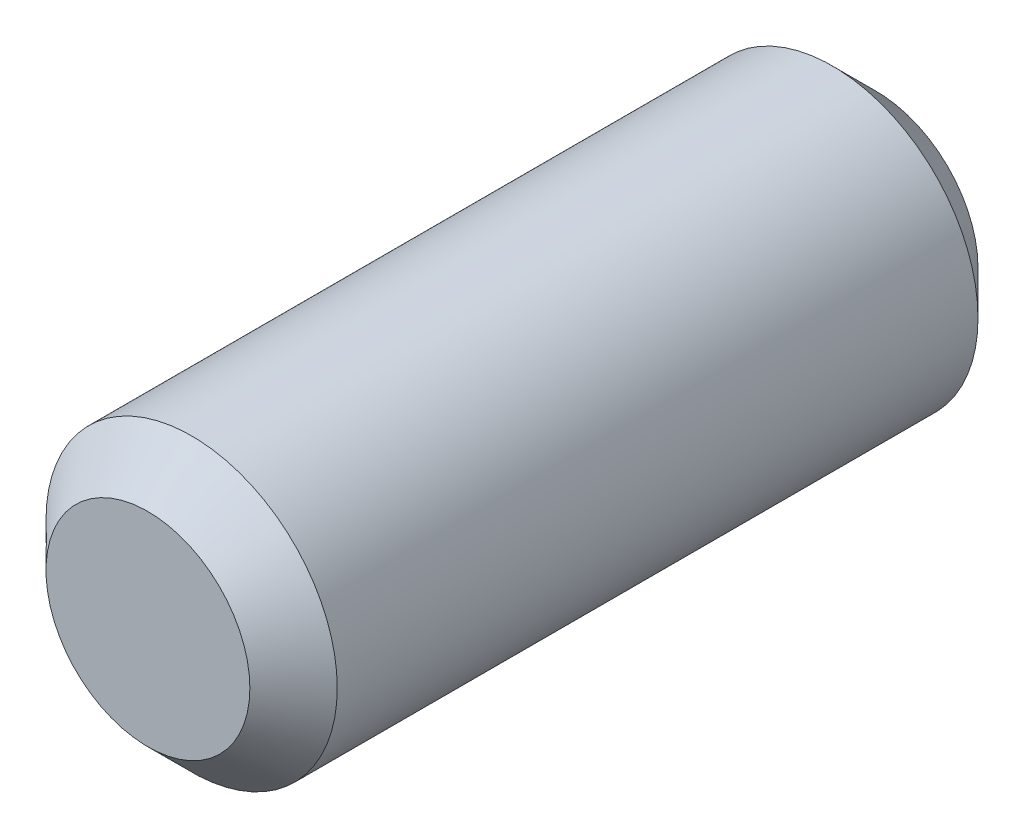
SolidWorks part; units mm, degrees
ref_plane "Plano frontal" through (0, 0, 0) normal (0, 0, 1) x (1, 0, 0)
ref_plane "Plano superior" through (0, 0, 0) normal (0, 1, 0) x (1, 0, 0)
ref_plane "Plano direito" through (0, 0, 0) normal (1, 0, 0) x (0, 0, -1)
sketch "Esboço1" plane through (0, 0, 0) normal (0, 0, 1) x (1, 0, 0)
  circle A0 centre (0, 0) radius 1
  dimension "D1" = 2
extrude "Ressalto-extrusão1" add sketch "Esboço1" along normal blind 2.5 and the other way blind 2.5
chamfer "Chanfro1" distance 0.3 angle 45 2 edges at (1, 0, -2.5) (1, 0, 2.5)
